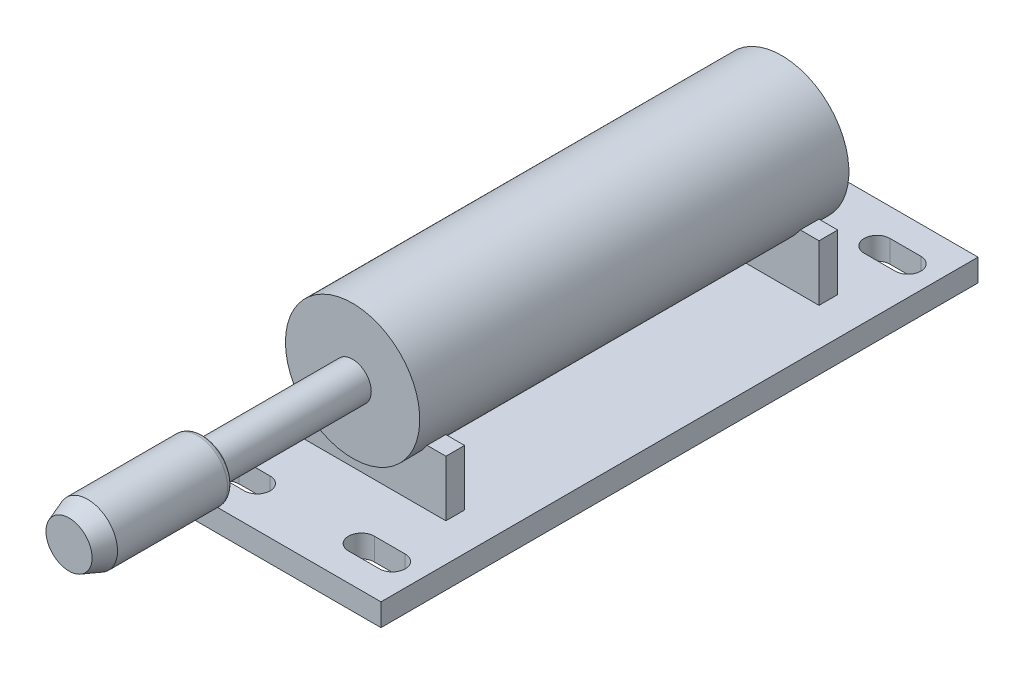
SolidWorks part; units mm, degrees
ref_plane "Front Plane" through (0, 0, 0) normal (0, 0, 1) x (1, 0, 0)
ref_plane "Top Plane" through (0, 0, 0) normal (0, 1, 0) x (1, 0, 0)
ref_plane "Right Plane" through (0, 0, 0) normal (1, 0, 0) x (0, 0, -1)
sketch "Sketch1" plane through (0, 0, 0) normal (0, 1, 0) x (1, 0, 0)
  line L0 (30.1, 160) -> (30.1, 0) construction
  line L1 (0, 0) -> (60.2, 0)
  line L2 (0, 0) -> (0, 160)
  line L3 (0, 160) -> (60.2, 160)
  line L4 (60.2, 0) -> (60.2, 160)
  line L5 (7.85, 152.55) -> (16.15, 152.55)
  line L7 (7.85, 145.65) -> (16.15, 145.65)
  line L9 (60.2, 80) -> (0, 80) construction
  line L10 (52.35, 145.65) -> (44.05, 145.65)
  line L11 (52.35, 152.55) -> (44.05, 152.55)
  line L12 (52.35, 7.45) -> (44.05, 7.45)
  line L13 (52.35, 14.35) -> (44.05, 14.35)
  line L14 (7.85, 14.35) -> (16.15, 14.35)
  line L15 (7.85, 7.45) -> (16.15, 7.45)
  line L16 (16.15, 149.1) -> (16.15, 10.9) construction
  line L17 (16.15, 149.1) -> (44.05, 149.1) construction
  arc A0 (7.85, 152.55) -> (7.85, 145.65) centre (7.85, 149.1) ccw
  arc A1 (16.15, 145.65) -> (16.15, 152.55) centre (16.15, 149.1) ccw
  arc A2 (52.35, 152.55) -> (52.35, 145.65) centre (52.35, 149.1) cw
  arc A3 (44.05, 145.65) -> (44.05, 152.55) centre (44.05, 149.1) cw
  arc A4 (44.05, 14.35) -> (44.05, 7.45) centre (44.05, 10.9) ccw
  arc A5 (52.35, 7.45) -> (52.35, 14.35) centre (52.35, 10.9) ccw
  arc A6 (7.85, 7.45) -> (7.85, 14.35) centre (7.85, 10.9) cw
  arc A7 (16.15, 14.35) -> (16.15, 7.45) centre (16.15, 10.9) cw
  dimension "D6" = 8.3
  dimension "D4" = 7.85
  dimension "D1" = 60.2
  dimension "D2" = 160
  dimension "D3" = 7.45
  dimension "D5" = 6.9
  dimension "D7" = 27.9
  dimension "D8" = 138.2
extrude "Boss-Extrude1" add sketch "Sketch1" along normal blind 6
sketch "Sketch2" plane through (0, 0, 0) normal (0, -1, 0) x (-1, 0, 0)
  line L0 (-52.35, 152.55) -> (-44.05, 152.55) construction
  line L1 (-44.05, 145.65) -> (-52.35, 145.65) construction
  line L2 (-16.15, 152.55) -> (-7.85, 152.55) construction
  line L3 (-7.85, 145.65) -> (-16.15, 145.65) construction
  line L4 (0, 0) -> (0, 160)
  line L5 (0, 160) -> (-60.2, 160)
  line L6 (-60.2, 160) -> (-60.2, 0)
  line L7 (-60.2, 0) -> (0, 0)
  line L8 (0, 0) -> (0, 160)
  line L9 (0, 160) -> (-60.2, 160)
  line L10 (-60.2, 160) -> (-60.2, 0)
  line L11 (-60.2, 0) -> (0, 0)
  line L12 (-52.35, 14.35) -> (-44.05, 14.35) construction
  line L13 (-44.05, 7.45) -> (-52.35, 7.45) construction
  line L14 (-16.15, 14.35) -> (-7.85, 14.35) construction
  line L15 (-7.85, 7.45) -> (-16.15, 7.45) construction
  line L16 (-52.35, 152.55) -> (-44.05, 152.55)
  line L17 (-44.05, 145.65) -> (-52.35, 145.65)
  line L18 (-16.15, 152.55) -> (-7.85, 152.55)
  line L19 (-7.85, 145.65) -> (-16.15, 145.65)
  line L20 (-52.35, 14.35) -> (-44.05, 14.35)
  line L21 (-44.05, 7.45) -> (-52.35, 7.45)
  line L22 (-16.15, 14.35) -> (-7.85, 14.35)
  line L23 (-7.85, 7.45) -> (-16.15, 7.45)
  arc A0 (-52.35, 152.55) -> (-52.35, 145.65) centre (-52.35, 149.1) ccw construction
  arc A1 (-44.05, 145.65) -> (-44.05, 152.55) centre (-44.05, 149.1) ccw construction
  arc A2 (-7.85, 145.65) -> (-7.85, 152.55) centre (-7.85, 149.1) ccw construction
  arc A3 (-16.15, 152.55) -> (-16.15, 145.65) centre (-16.15, 149.1) ccw construction
  arc A4 (-52.35, 14.35) -> (-52.35, 7.45) centre (-52.35, 10.9) ccw construction
  arc A5 (-44.05, 7.45) -> (-44.05, 14.35) centre (-44.05, 10.9) ccw construction
  arc A6 (-16.15, 14.35) -> (-16.15, 7.45) centre (-16.15, 10.9) ccw construction
  arc A7 (-7.85, 7.45) -> (-7.85, 14.35) centre (-7.85, 10.9) ccw construction
  arc A8 (-52.35, 152.55) -> (-52.35, 145.65) centre (-52.35, 149.1) ccw
  arc A9 (-44.05, 145.65) -> (-44.05, 152.55) centre (-44.05, 149.1) ccw
  arc A10 (-7.85, 145.65) -> (-7.85, 152.55) centre (-7.85, 149.1) ccw
  arc A11 (-16.15, 152.55) -> (-16.15, 145.65) centre (-16.15, 149.1) ccw
  arc A12 (-52.35, 14.35) -> (-52.35, 7.45) centre (-52.35, 10.9) ccw
  arc A13 (-44.05, 7.45) -> (-44.05, 14.35) centre (-44.05, 10.9) ccw
  arc A14 (-16.15, 14.35) -> (-16.15, 7.45) centre (-16.15, 10.9) ccw
  arc A15 (-7.85, 7.45) -> (-7.85, 14.35) centre (-7.85, 10.9) ccw
  dimension "D1" = 0
sketch "Sketch3" plane through (0, 6, 0) normal (0, 1, 0) x (1, 0, 0)
  line L0 (30.1, 160) -> (30.1, 130) construction
  line L1 (60.2, 160) -> (0, 160) construction
  line L2 (0, 80) -> (60.2, 80) construction
  line L3 (10.1, 127.5) -> (50.1, 127.5)
  line L4 (10.1, 127.5) -> (10.1, 132.5)
  line L5 (10.1, 132.5) -> (50.1, 132.5)
  line L6 (50.1, 127.5) -> (50.1, 132.5)
  line L7 (10.1, 127.5) -> (50.1, 132.5) construction
  line L8 (10.1, 132.5) -> (50.1, 127.5) construction
  line L9 (0, 160) -> (0, 0) construction
  line L10 (60.2, 0) -> (60.2, 160) construction
  line L11 (50.1, 32.5) -> (50.1, 27.5)
  line L12 (10.1, 32.5) -> (50.1, 32.5)
  line L13 (10.1, 27.5) -> (50.1, 27.5)
  line L14 (10.1, 32.5) -> (10.1, 27.5)
  dimension "D1" = 40
  dimension "D2" = 5
  dimension "D3" = 30
extrude "Boss-Extrude2" add sketch "Sketch3" along normal blind 15
sketch "Sketch4" plane through (0, 0, -132.5) normal (0, 0, -1) x (-1, 0, 0)
  line L0 (-30.1, 21) -> (-30.1, 31) construction
  line L1 (-50.1, 21) -> (-10.1, 21) construction
  circle A0 centre (-30.1, 31) radius 18
  dimension "D1" = 36
  dimension "D2" = 10
extrude "Boss-Extrude3" add sketch "Sketch4" along normal blind 5 and the other way offset from surface (110 mm away) 5 other way up to face at (30.1, 13.5, -27.5)
sketch "Sketch5" plane through (0, 0, -22.5) normal (0, 0, 1) x (1, 0, 0)
  circle A0 centre (30.1, 31) radius 5
  dimension "D1" = 10
extrude "Boss-Extrude4" add sketch "Sketch5" along normal blind 40
sketch "Sketch6" plane through (0, 0, 17.5) normal (0, 0, 1) x (1, 0, 0)
  circle A0 centre (30.1, 31) radius 8
  dimension "D1" = 16
extrude "Boss-Extrude5" add sketch "Sketch6" along normal blind 36
chamfer "Chamfer1" distance 5 angle 20 1 edges at (38.1, 31, 53.5)
fillet "Fillet1" radius 1.5 2 edges at (35.1, 31, 17.5) (38.1, 31, 17.5)
